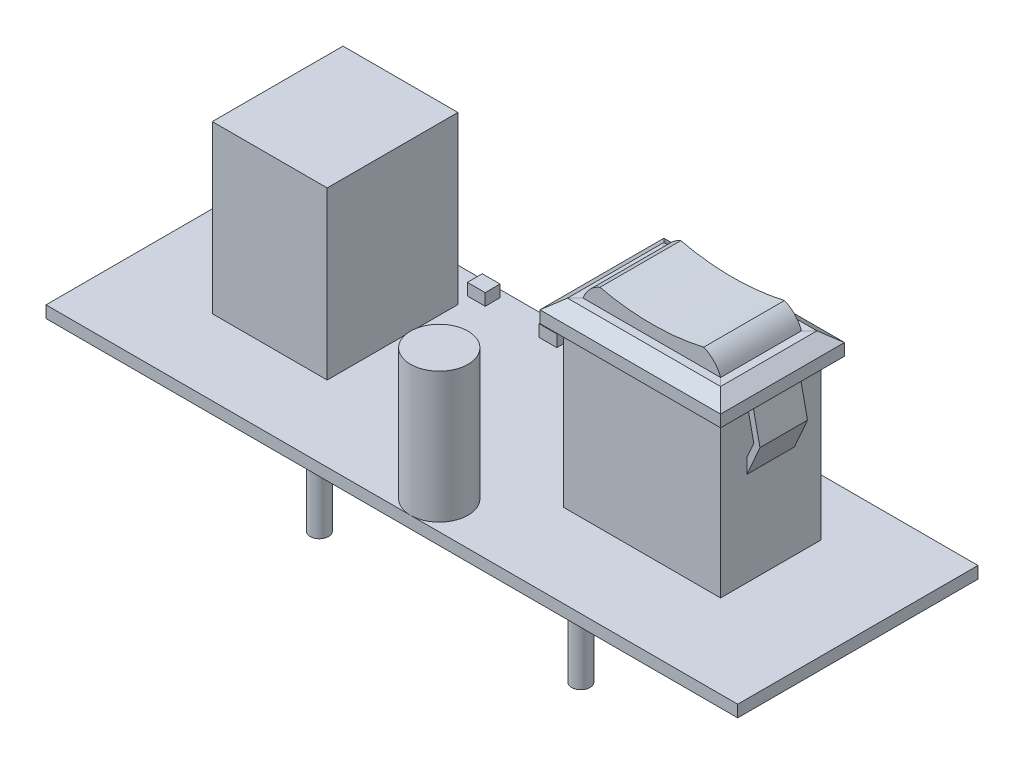
SolidWorks part; units mm, degrees
note: '?' marks a value the reader was unsure of.
ref_plane "Front Plane" through (0, 0, 0) normal (0, 0, 1) x (1, 0, 0)
ref_plane "Top Plane" through (0, 0, 0) normal (0, 1, 0) x (1, 0, 0)
ref_plane "Right Plane" through (0, 0, 0) normal (1, 0, 0) x (0, 0, -1)
sketch "Sketch1" plane through (0, 0, 0) normal (0, 1, 0) x (1, 0, 0)
  line L1 (-29.1, -10.11) -> (29.1, -10.11)
  line L2 (-29.1, -10.11) -> (-29.1, 10.11)
  line L3 (-29.1, 10.11) -> (29.1, 10.11)
  line L4 (29.1, -10.11) -> (29.1, 10.11)
  line L5 (-29.1, -10.11) -> (29.1, 10.11) construction
  line L6 (-29.1, 10.11) -> (29.1, -10.11) construction
  point P0 (0, 0)
  dimension "D1" = 20.22
  dimension "D2" = 58.2
extrude "Boss-Extrude1" add sketch "Sketch1" along normal blind 1
sketch "Sketch2" plane through (0, 1, 0) normal (0, 1, 0) x (1, 0, 0)
  line L0 (29.1, 10.11) -> (-29.1, 10.11) construction
  line L1 (-21.46, -3.76) -> (-11.79, -3.76)
  line L2 (-21.46, -3.76) -> (-21.46, 7.24)
  line L3 (-21.46, 7.24) -> (-11.79, 7.24)
  line L4 (-11.79, -3.76) -> (-11.79, 7.24)
  line L5 (-29.1, 10.11) -> (-29.1, -10.11) construction
  dimension "D1" = 9.67
  dimension "D2" = 11
  dimension "D3" = 2.87
  dimension "D4" = 7.64
extrude "Boss-Extrude2" add sketch "Sketch2" along normal blind 14 and the other way offset from surface (5.2 mm away) 4.2 other way up to face at (0, 0, 0)
sketch "Sketch3" plane through (0, 1, 0) normal (0, 1, 0) x (1, 0, 0)
  line L1 (-29.1, -10.11) -> (29.1, -10.11) construction
  line L2 (29.1, -10.11) -> (29.1, 10.11) construction
  circle A0 centre (1.57, -7.69) radius 2.42
  point P2 (-0.85, -7.69)
  point P3 (3.99, -7.69)
  dimension "D1" = 4.84
  dimension "D2" = 25.11
extrude "Boss-Extrude3" add sketch "Sketch3" along normal blind 11
sketch "Sketch4" plane through (0, 1, 0) normal (0, 1, 0) x (1, 0, 0)
  line L0 (29.1, -10.11) -> (29.1, 10.11) construction
  line L1 (7.44, -3.09) -> (20.64, -3.09)
  line L2 (7.44, -3.09) -> (7.44, 5.34)
  line L3 (7.44, 5.34) -> (20.64, 5.34)
  line L4 (20.64, -3.09) -> (20.64, 5.34)
  line L5 (29.1, 10.11) -> (-29.1, 10.11) construction
  dimension "D1" = 13.2
  dimension "D2" = 8.43
  dimension "D3" = 8.46
  dimension "D4" = 4.77
extrude "Boss-Extrude4" add sketch "Sketch4" along normal blind 13.4 and the other way offset from surface (4.3 mm away) 3.3 other way up to face at (-16.625, 0, -1.74)
sketch "Sketch5" plane through (7.44, 0, 0) normal (-1, 0, 0) x (0, 0, 1)
  line L0 (3.09, 14.4) -> (4.09, 14.4)
  line L1 (4.09, 14.4) -> (4.09, 15.4)
  line L2 (4.09, 15.4) -> (2.93, 16.25)
  line L3 (2.93, 16.25) -> (2.275, 16.25)
  line L4 (2.275, 16.25) -> (2.275, 14.4)
  line L5 (3.09, 14.4) -> (-5.34, 14.4) construction
  line L6 (2.275, 14.4) -> (3.09, 14.4)
  line L7 (4.09, 14.4) -> (-6.34, 14.4) construction
  line L8 (2.93, 16.25) -> (-5.18, 16.25) construction
  line L9 (-1.125, 14.4) -> (-1.125, 16.25) construction
  line L10 (2.275, 15.325) -> (-4.525, 15.325) construction
  point P10 (-1.125, 14.4)
  point P16 (-1.125, 15.325)
  point P17 (0, 0)
  dimension "D1" = 10.43
  dimension "D2" = 8.11
  dimension "D3" = 1.85
  dimension "D5" = 1
  dimension "D6" = 6.8
sketch "Sketch6" plane through (0, 14.4, 0) normal (0, 1, 0) x (1, 0, 0)
  line L4 (7.44, 5.34) -> (7.44, -3.09)
  line L5 (7.44, -3.09) -> (20.64, -3.09)
  line L6 (20.64, -3.09) -> (20.64, 5.34)
  line L7 (20.64, 5.34) -> (7.44, 5.34)
  line L8 (7.44, 5.34) -> (7.44, -3.09)
  line L9 (7.44, -3.09) -> (20.64, -3.09)
  line L10 (20.64, -3.09) -> (20.64, 5.34)
  line L11 (20.64, 5.34) -> (7.44, 5.34)
  dimension "D1" = 0
sweep "Sweep1" add profiles "Sketch5" path "Sketch6"
sketch "Sketch7" plane through (0, 14.4, 0) normal (0, 1, 0) x (1, 0, 0)
  line L4 (19.825, 4.525) -> (8.255, 4.525)
  line L5 (8.255, 4.525) -> (8.255, -2.275)
  line L6 (8.255, -2.275) -> (19.825, -2.275)
  line L7 (19.825, -2.275) -> (19.825, 4.525)
  line L8 (19.825, 4.525) -> (8.255, 4.525)
  line L9 (8.255, 4.525) -> (8.255, -2.275)
  line L10 (8.255, -2.275) -> (19.825, -2.275)
  line L11 (19.825, -2.275) -> (19.825, 4.525)
  dimension "D1" = 0
extrude "Boss-Extrude5" add sketch "Sketch7" along normal offset from surface (3.35 mm away) 1.5 up to face at (14.04, 16.25, 2.6025) offset beyond the face yes
sketch "Sketch8" plane through (0, 0, -4.525) normal (0, 0, -1) x (-1, 0, 0)
  line L0 (-8.255, 17.75) -> (-19.825, 17.75) construction
  line L1 (-14.04, 17.25) -> (-14.04, 17.75) construction
  line L4 (-8.255, 17.75) -> (-8.255, 16.25) construction
  line L5 (-19.825, 17.75) -> (-19.825, 16.25) construction
  line L6 (-8.255, 17.75) -> (-8.255, 16.25)
  line L7 (-8.255, 17.75) -> (-19.825, 17.75)
  line L8 (-19.825, 17.75) -> (-19.825, 16.25)
  arc A0 (-19.825, 16.25) -> (-18.405, 17.75) centre (-17.4616, 15.4348) cw
  arc A1 (-18.405, 17.75) -> (-9.675, 17.75) centre (-14.04, 36.5532) ccw
  arc A2 (-8.255, 16.25) -> (-9.675, 17.75) centre (-10.6184, 15.4348) ccw
  point P13 (-18.4505, 17.75)
  point P14 (-8.255, 16.25)
  point P15 (-9.675, 17.75)
  line M3 (-19.825, 17.75) -> (-19.825, 16.25)
  line M5 (-8.255, 16.25) -> (-8.255, 17.75)
  line M6 (-8.255, 17.75) -> (-19.825, 17.75)
  dimension "D1" = 0.5
  dimension "D3" = 2.5
  dimension "D2" = 8.73
extrude "Cut-Extrude1" cut sketch "Sketch8" against normal through all both and the other way through all contours A0 L7 M3 | A1 L1 M6 | L1 A1 L7 | A2 M5 M6
ref_plane "Plane1" through (0, 0, -1.125) normal (0, 0, -1) x (-1, 0, 0)
ref_plane "Plane2" through (14.04, 0, 0) normal (1, 0, 0) x (0, 0, -1)
sketch "Sketch9" plane through (0, 0, -1.125) normal (0, 0, -1) x (-1, 0, 0)
  line L0 (-21.1, 14.4) -> (-21.74, 11.4)
  line L1 (-21.64, 14.4) -> (-6.44, 14.4) construction
  line L2 (-21.74, 11.4) -> (-19.7889, 6.9657)
  line L4 (-21.1, 14.4) -> (-6.98, 14.4) construction
  line L5 (-21.74, 11.4) -> (-6.34, 11.4) construction
  line L6 (-14.04, 14.4) -> (-14.04, 11.4) construction
  line L7 (-20.64, 14.4) -> (-7.44, 14.4) construction
  line L8 (-20.64, 14.4) -> (-20.64, 1) construction
  line L9 (-21.1, 14.4) -> (-20.9889, 14.921)
  point P5 (-20.64, 8.9)
  point P8 (-14.04, 14.4)
  dimension "D1" = 15.4
  dimension "D2" = 14.12
  dimension "D3" = 3
  dimension "D4" = 2.5
extrude "Extrude-Thin2" add sketch "Sketch9" along normal mid plane 4 thin thin type one direction reverse wall 0.5
mirror "Mirror1" about plane through (14.04, 0, 0) normal (1, 0, 0) of "Extrude-Thin2"
sketch "Sketch10" plane through (0, 0, 0) normal (0, -1, 0) x (1, 0, 0)
  line L0 (-10.1, 6.11) -> (11.9, 6.11) construction
  line L1 (-29.1, -10.11) -> (-29.1, 10.11) construction
  line L2 (-29.1, 10.11) -> (29.1, 10.11) construction
  circle A0 centre (-10.1, 6.11) radius 0.775
  circle A1 centre (11.9, 6.11) radius 0.775
  dimension "D1" = 1.55
  dimension "D2" = 22
  dimension "D3" = 19
  dimension "D4" = 4
extrude "Boss-Extrude6" add sketch "Sketch10" along normal blind 8
sketch "Sketch11" plane through (0, 15, 0) normal (0, 1, 0) x (1, 0, 0)
  line L0 (-21.46, 7.24) -> (-11.79, 7.24) construction
  line L1 (-16.625, 5.86) -> (-16.625, 7.24) construction
  circle A0 centre (-16.625, 2.685) radius 3.175
  point P4 (-16.625, 2.685)
  point P5 (-16.625, 5.86)
  dimension "D1" = 6.35
  dimension "D2" = 1.38
ref_axis "Axis1" through (-16.625, -4.4, -2.685) along (0, 1, 0)?
sketch "Sketch12" plane through (0, 1, 0) normal (0, 1, 0) x (1, 0, 0)
  line L1 (-18.04, 9.51) -> (-16.54, 9.51)
  line L2 (-18.04, 9.51) -> (-18.04, 8.26)
  line L3 (-18.04, 8.26) -> (-16.54, 8.26)
  line L4 (-16.54, 9.51) -> (-16.54, 8.26)
  line L5 (-12.015, 9.51) -> (-12.015, 8.26)
  line L6 (-12.015, 9.51) -> (-10.515, 9.51)
  line L7 (-10.515, 9.51) -> (-10.515, 8.26)
  line L8 (-12.015, 8.26) -> (-10.515, 8.26)
  line L9 (-5.99, 9.51) -> (-5.99, 8.26)
  line L10 (-5.99, 9.51) -> (-4.49, 9.51)
  line L11 (-4.49, 9.51) -> (-4.49, 8.26)
  line L12 (-5.99, 8.26) -> (-4.49, 8.26)
  line L13 (0.035, 9.51) -> (0.035, 8.26)
  line L14 (0.035, 9.51) -> (1.535, 9.51)
  line L15 (1.535, 9.51) -> (1.535, 8.26)
  line L16 (0.035, 8.26) -> (1.535, 8.26)
  line L17 (6.06, 9.51) -> (6.06, 8.26)
  line L18 (6.06, 9.51) -> (7.56, 9.51)
  line L19 (7.56, 9.51) -> (7.56, 8.26)
  line L20 (6.06, 8.26) -> (7.56, 8.26)
  line L22 (-29.1, 10.11) -> (-29.1, -10.11) construction
  line L23 (29.1, 10.11) -> (-29.1, 10.11) construction
  point P4 (-18.04, 10.11)
  point P5 (-18.0273, 9.6136)
  dimension "D1" = 5
  dimension "D2" = 1.5
  dimension "D3" = 1.25
  dimension "D4" = 25.6
  dimension "D5" = 11.06
  dimension "D6" = 0.6
extrude "Boss-Extrude7" add sketch "Sketch12" along normal blind 1
